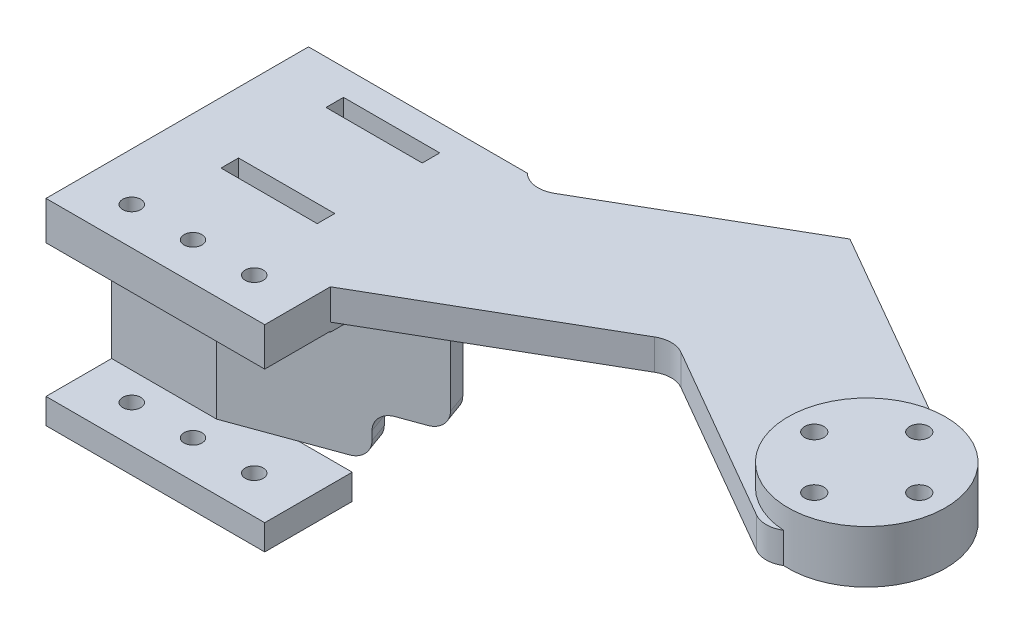
SolidWorks part; units mm, degrees
ref_plane "前视基准面" through (0, 0, 0) normal (0, 0, 1) x (1, 0, 0)
ref_plane "上视基准面" through (0, 0, 0) normal (0, 1, 0) x (1, 0, 0)
ref_plane "右视基准面" through (0, 0, 0) normal (1, 0, 0) x (0, 0, -1)
other "Configuration Table"
sketch "草图1" plane through (0, 0, 0) normal (0, 1, 0) x (1, 0, 0)
  line L1 (0, 0) -> (25, 0)
  line L2 (0, 0) -> (0, -10)
  line L3 (0, -10) -> (25, -10)
  line L4 (25, 0) -> (25, -10)
  dimension "D1" = 10
  dimension "D2" = 25
extrude "凸台-拉伸1" add sketch "草图1" along normal blind 22.5
sketch "草图2" plane through (0, 0, 10) normal (0, 0, 1) x (1, 0, 0)
  line L0 (0, 22.5) -> (0, 0) construction
  line L1 (0, 10.5) -> (6.5085, 10.5) construction
  line L2 (25, 22.5) -> (25, 0) construction
  line L3 (0, 18.1) -> (25, 18.1)
  line L4 (0, 18.1) -> (0, 2.9)
  line L5 (0, 2.9) -> (25, 2.9)
  line L6 (25, 18.1) -> (25, 2.9)
  line L7 (0, 18.1) -> (25, 2.9) construction
  line L8 (0, 22.5) -> (25, 22.5) construction
  point P4 (12.5, 10.5)
  point P12 (0, 11.25)
  dimension "D1" = 15.2
  dimension "D2" = 12
extrude "切除-拉伸1" cut sketch "草图2" against normal blind 7.5
sketch "草图4" plane through (0, 22.5, 0) normal (0, 1, 0) x (1, 0, 0)
  line L0 (12.5, -5.7) -> (19.5, -5.7) construction
  line L1 (12.5, -5.7) -> (5.5, -5.7) construction
  line L2 (0, -10) -> (25, -10) construction
  line L3 (25, 0) -> (0, 0) construction
  line L4 (12.5, -10) -> (12.5, -4.7527) construction
  circle A3 centre (12.5, -5.7) radius 1.03
  circle A4 centre (19.5, -5.7) radius 1.03
  circle A5 centre (5.5, -5.7) radius 1.03
  point P0 (12.5, -10)
  point P1 (12.5, -5.7)
  dimension "D3" = 7
  dimension "D2" = 7
  dimension "D1" = 5.7
extrude "切除-拉伸2" cut sketch "草图4" against normal through all both and the other way through all
sketch "草图5" plane through (0, 0, 0) normal (0, 0, -1) x (-1, 0, 0)
  line L0 (-25, 22.5) -> (0, 22.5) construction
  line L1 (-25, 22.5) -> (0, 22.5)
  line L2 (-25, 22.5) -> (-25, 18)
  line L3 (-25, 18) -> (0, 18)
  line L4 (0, 22.5) -> (0, 18)
  line L5 (-25, 22.5) -> (-25, 0) construction
  line L6 (0, 22.5) -> (0, 0) construction
  dimension "D1" = 4.5
extrude "凸台-拉伸2" add sketch "草图5" along normal blind 20
sketch "草图6" plane through (0, 22.5, 0) normal (0, 1, 0) x (1, 0, 0)
  line L0 (0, 10) -> (25, 10) construction
  line L1 (0, 20) -> (0, -10) construction
  line L2 (25, -10) -> (25, 20) construction
  line L3 (0, 20) -> (25, 20) construction
  line L4 (12.5, -10) -> (12.5, -7.6427) construction
  line L5 (7, 17) -> (18, 17)
  line L6 (7, 17) -> (7, 15)
  line L7 (7, 15) -> (18, 15)
  line L8 (18, 17) -> (18, 15)
  line L9 (7, 17) -> (18, 15) construction
  line L10 (7, 15) -> (18, 17) construction
  line L11 (7, 5) -> (18, 5)
  line L12 (7, 5) -> (7, 3)
  line L13 (7, 3) -> (18, 3)
  line L14 (18, 5) -> (18, 3)
  line L15 (7, 5) -> (18, 3) construction
  line L16 (7, 3) -> (18, 5) construction
  point P8 (12.5, 16)
  point P9 (12.5, 4)
  point P10 (12.5, 16)
  point P15 (12.5, 4)
  dimension "D1" = 10
  dimension "D2" = 6
  dimension "D3" = 6
  dimension "D4" = 2
  dimension "D5" = 11
  dimension "D6" = 11
  dimension "D7" = 2
extrude "切除-拉伸3" cut sketch "草图6" against normal up to surface (4.5 mm away) up to face at (12.5, 18, -10)
sketch "草图9" plane through (0, 0, 0) normal (-1, 0, 0) x (0, 0, 1)
  line L0 (2.5, 18.1) -> (2.5, 22.5) construction
  line L1 (-20, 22.5) -> (10, 22.5) construction
sketch "草图14" plane through (25, 0, 0) normal (1, 0, 0) x (0, 0, -1)
  line L0 (-2.5, 18.1) -> (-2.5, 22.5) construction
  line L1 (-10, 22.5) -> (20, 22.5) construction
sketch "草图15" plane through (0, 22.5, 0) normal (0, 1, 0) x (1, 0, 0)
  line L0 (25, -2.5) -> (50, 11.9338)
  line L1 (50, 11.9338) -> (75, -2.5)
  line L2 (25, -2.5) -> (75, -2.5) construction
  line L3 (25, 17.5) -> (49.9672, 31.9148)
  line L4 (25, -10) -> (25, 20) construction
  line L5 (49.9672, 31.9148) -> (75, 17.5)
  line L6 (75, 17.5) -> (75, -2.5)
  line L7 (25, 17.5) -> (25, -2.5)
  dimension "D1" = 50
  dimension "D2" = 30
  dimension "D3" = 30
  dimension "D4" = 20
extrude "凸台-拉伸3" add sketch "草图15" against normal blind 3.5
sketch "草图16" plane through (0, 19, 0) normal (0, -1, 0) x (1, 0, 0)
  circle A0 centre (75.5215, -8.2821) radius 9
  point P0 (75.5215, -8.2821)
  point P1 (75.5215, -8.2821)
extrude "凸台-拉伸4" add sketch "草图16" against normal blind 6
fillet "圆角1" radius 3 3 edges at (50, 20.75, -11.9338) (25, 20.75, -17.5) (75, 20.75, 2.5)
sketch "草图17" plane through (0, 19, 0) normal (0, -1, 0) x (1, 0, 0)
  circle A0 centre (75.5215, -8.2821) radius 6 construction
  circle A1 centre (75.5215, -14.2821) radius 1.1
  circle A2 centre (75.5215, -2.2821) radius 1.1
  circle A3 centre (69.5215, -8.2821) radius 1.1
  circle A4 centre (81.5215, -8.2821) radius 1.1
extrude "切除-拉伸4" cut sketch "草图17" against normal up to next
sketch "草图18" plane through (25, 0, 0) normal (1, 0, 0) x (0, 0, -1)
  line L0 (-2.5, 2.9) -> (0, 2.9) construction
  line L1 (0, 18) -> (0, 0) construction
  line L2 (0, 18) -> (-2.5, 18) construction
  line L3 (-2.5, 2.9) -> (-2.5, 18.1) construction
  point P6 (0, 2.9)
  point P12 (0, 18)
sketch "草图19" plane through (0, 0, 0) normal (0, 0, -1) x (-1, 0, 0)
  line L0 (-25, 18) -> (0, 18) construction
  line L1 (-25, 2.9) -> (0, 2.9)
  line L2 (-25, 2.9) -> (-25, 18)
  line L3 (-25, 18) -> (0, 18)
  line L4 (0, 2.9) -> (0, 18) construction
  line L5 (-12, 2.9) -> (-12, 18)
  line L6 (0, 18) -> (0, 0) construction
  line L8 (-25, 18) -> (-12, 18)
  line L9 (-25, 18) -> (-25, 2.9)
  line L10 (-25, 2.9) -> (-12, 2.9)
  line L11 (-12, 18) -> (-12, 2.9)
  line M4 (-25, 18) -> (-25, 0)
  dimension "D1" = 12
extrude "切除-拉伸5" cut sketch "草图19" against normal blind 10 contours L1 L5 L3 M4 region at (18.5, 10.45, 0)
sketch "草图21" plane through (0, 2.9, 0) normal (0, 1, 0) x (1, 0, 0)
  line L0 (12, -2.5) -> (12, 0)
  line L1 (12, -2.5) -> (31.5973, 4.6328)
  line L2 (25, -2.5) -> (12, -2.5) construction
  line L3 (12, 0) -> (30.7939, 6.8404)
  line L4 (30.7939, 6.8404) -> (31.5973, 4.6328)
  dimension "D1" = 20
  dimension "D2" = 20
extrude "凸台-拉伸5" add sketch "草图21" along normal up to surface (16.1 mm away) up to face at (75.5215, 19, -15.3821)
sketch "草图22" plane through (2.2072, 0, 6.0643) normal (0.342, 0, 0.9397) x (0.9397, 0, -0.342)
  line L1 (31.2763, 2.9) -> (24.2763, 2.9)
  line L2 (31.2763, 2.9) -> (31.2763, 7.9)
  line L3 (31.2763, 7.9) -> (24.2763, 7.9)
  line L4 (24.2763, 2.9) -> (24.2763, 7.9)
  dimension "D1" = 5
  dimension "D2" = 7
extrude "切除-拉伸6" cut sketch "草图22" against normal up to next
fillet "圆角3" radius 2 3 edges at (31.1956, 7.9, -5.7366) (24.6177, 7.9, -3.3425) (24.6177, 2.9, -3.3425)
